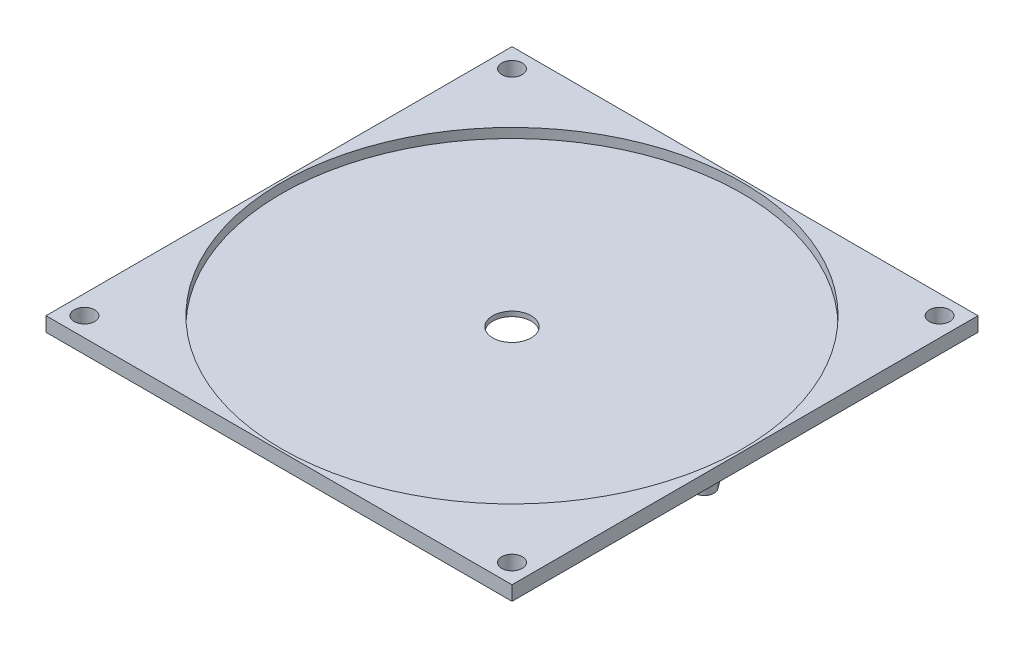
SolidWorks part; units mm, degrees
ref_plane "Front Plane" through (0, 0, 0) normal (0, 0, 1) x (1, 0, 0)
ref_plane "Top Plane" through (0, 0, 0) normal (0, 1, 0) x (1, 0, 0)
ref_plane "Right Plane" through (0, 0, 0) normal (1, 0, 0) x (0, 0, -1)
sketch "Sketch2" plane through (0, 0, 0) normal (0, 1, 0) x (1, 0, 0)
  line L1 (0, 0) -> (154.0002, 0)
  line L2 (0, 0) -> (0, 154.0002)
  line L3 (0, 154.0002) -> (154.0002, 154.0002)
  line L4 (154.0002, 0) -> (154.0002, 154.0002)
  dimension "D1" = 154.0002
  dimension "D2" = 154.0002
extrude "Boss-Extrude1" add sketch "Sketch2" along normal blind 4.7625
sketch "Sketch4" plane through (0, 4.7625, 0) normal (0, 1, 0) x (1, 0, 0)
  line L0 (0, 154.0002) -> (154.0002, 0) construction
  line L1 (0, 0) -> (154.0002, 154.0002) construction
  circle A0 centre (77.0001, 77.0001) radius 76.2
  dimension "D1" = 152.4
extrude "Cut-Extrude1" cut sketch "Sketch4" against normal blind 3.175
sketch "Sketch5" plane through (0, 4.7625, 0) normal (0, 1, 0) x (1, 0, 0)
  line L0 (6.35, 154.0002) -> (6.35, 147.6502) construction
  line L1 (154.0002, 154.0002) -> (0, 154.0002) construction
  line L3 (147.6502, 147.6502) -> (154.0002, 147.6502) construction
  line L4 (0, 154.0002) -> (0, 0) construction
  line L5 (154.0002, 0) -> (154.0002, 154.0002) construction
  line L6 (147.6502, 154.0002) -> (147.6502, 147.6502) construction
  line L7 (0, 147.6502) -> (6.35, 147.6502) construction
  line L8 (0, 6.35) -> (6.35, 6.35) construction
  line L9 (6.35, 6.35) -> (6.35, 0) construction
  line L10 (0, 0) -> (154.0002, 0) construction
  line L11 (147.6502, 0) -> (147.6502, 6.35) construction
  line L12 (147.6502, 6.35) -> (154.0002, 6.35) construction
  circle A0 centre (6.35, 6.35) radius 3.3782
  circle A1 centre (6.35, 147.6502) radius 3.3782
  circle A2 centre (147.6502, 147.6502) radius 3.3782
  circle A3 centre (147.6502, 6.35) radius 3.3782
  dimension "D8" = 6.7564
  dimension "D9" = 6.7564
  dimension "D10" = 6.7564
  dimension "D11" = 6.7564
  dimension "D1" = 6.35
  dimension "D2" = 6.35
  dimension "D3" = 6.35
  dimension "D4" = 6.35
  dimension "D5" = 6.35
  dimension "D6" = 6.35
  dimension "D7" = 6.35
extrude "Cut-Extrude2" cut sketch "Sketch5" against normal through all
sketch "Sketch7" plane through (0, 0, 0) normal (0, -1, 0) x (1, 0, 0)
  line L2 (96.0521, -88.4109) -> (110.1169, -69.3609)
  line L3 (109.2842, -89.7001) -> (123.349, -89.7001)
  line L4 (126.524, -86.5251) -> (126.524, -67.4751)
  line L5 (120.7947, -65.5893) -> (106.7299, -84.6393)
  line L6 (109.2842, -89.7001) -> (123.349, -89.7001)
  line L7 (126.524, -86.5251) -> (126.524, -67.4751)
  line L8 (120.7947, -65.5893) -> (106.7299, -84.6393)
  line L9 (150.1137, -64.3001) -> (136.049, -64.3001)
  line L10 (132.874, -67.4751) -> (132.874, -86.5251)
  line L11 (138.6032, -88.4109) -> (152.668, -69.3609)
  line L12 (150.1137, -64.3001) -> (136.049, -64.3001)
  line L13 (132.874, -67.4751) -> (132.874, -86.5251)
  line L14 (138.6032, -88.4109) -> (152.668, -69.3609)
  line L15 (107.5626, -64.3001) -> (93.4979, -64.3001)
  line L16 (96.0521, -88.4109) -> (110.1169, -69.3609)
  line L17 (107.5626, -64.3001) -> (93.4979, -64.3001)
  line L18 (58.2758, -65.2116) -> (38.9091, -84.2616)
  line L19 (25.2516, -88.7886) -> (44.6183, -69.7386)
  line L20 (42.3918, -64.3001) -> (23.0251, -64.3001)
  line L21 (19.8501, -67.4751) -> (19.8501, -86.5251)
  line L22 (25.2516, -88.7886) -> (44.6183, -69.7386)
  line L23 (42.3918, -64.3001) -> (23.0251, -64.3001)
  line L24 (19.8501, -67.4751) -> (19.8501, -86.5251)
  line L25 (41.1355, -89.7001) -> (60.5023, -89.7001)
  line L26 (58.2758, -65.2116) -> (38.9091, -84.2616)
  line L27 (41.1355, -89.7001) -> (60.5023, -89.7001)
  arc A4 (106.7299, -84.6393) -> (109.2842, -89.7001) centre (109.2842, -86.5251) ccw
  arc A5 (123.349, -89.7001) -> (126.524, -86.5251) centre (123.349, -86.5251) ccw
  arc A6 (126.524, -67.4751) -> (120.7947, -65.5893) centre (123.349, -67.4751) ccw
  arc A7 (106.7299, -84.6393) -> (109.2842, -89.7001) centre (109.2842, -86.5251) ccw
  arc A8 (123.349, -89.7001) -> (126.524, -86.5251) centre (123.349, -86.5251) ccw
  arc A9 (126.524, -67.4751) -> (120.7947, -65.5893) centre (123.349, -67.4751) ccw
  arc A11 (152.668, -69.3609) -> (150.1137, -64.3001) centre (150.1137, -67.4751) ccw
  arc A12 (136.049, -64.3001) -> (132.874, -67.4751) centre (136.049, -67.4751) ccw
  arc A13 (132.874, -86.5251) -> (138.6032, -88.4109) centre (136.049, -86.5251) ccw
  arc A14 (152.668, -69.3609) -> (150.1137, -64.3001) centre (150.1137, -67.4751) ccw
  arc A15 (136.049, -64.3001) -> (132.874, -67.4751) centre (136.049, -67.4751) ccw
  arc A16 (132.874, -86.5251) -> (138.6032, -88.4109) centre (136.049, -86.5251) ccw
  arc A19 (93.4979, -64.3001) -> (90.7482, -69.0626) centre (93.4979, -67.4751) ccw
  arc A20 (90.7482, -84.9376) -> (90.7482, -69.0626) centre (77.0001, -77.0001) ccw
  arc A21 (90.7482, -84.9376) -> (96.0521, -88.4109) centre (93.4979, -86.5251) ccw
  arc A22 (110.1169, -69.3609) -> (107.5626, -64.3001) centre (107.5626, -67.4751) ccw
  arc A23 (93.4979, -64.3001) -> (90.7482, -69.0626) centre (93.4979, -67.4751) ccw
  arc A24 (90.7482, -84.9376) -> (90.7482, -69.0626) centre (77.0001, -77.0001) ccw
  arc A25 (90.7482, -84.9376) -> (96.0521, -88.4109) centre (93.4979, -86.5251) ccw
  arc A26 (110.1169, -69.3609) -> (107.5626, -64.3001) centre (107.5626, -67.4751) ccw
  arc A27 (19.8501, -86.5251) -> (25.2516, -88.7886) centre (23.0251, -86.5251) ccw
  arc A28 (44.6183, -69.7386) -> (42.3918, -64.3001) centre (42.3918, -67.4751) ccw
  arc A29 (23.0251, -64.3001) -> (19.8501, -67.4751) centre (23.0251, -67.4751) ccw
  arc A30 (19.8501, -86.5251) -> (25.2516, -88.7886) centre (23.0251, -86.5251) ccw
  arc A31 (44.6183, -69.7386) -> (42.3918, -64.3001) centre (42.3918, -67.4751) ccw
  arc A32 (23.0251, -64.3001) -> (19.8501, -67.4751) centre (23.0251, -67.4751) ccw
  arc A35 (60.5023, -89.7001) -> (63.2519, -84.9376) centre (60.5023, -86.5251) ccw
  arc A36 (63.2519, -69.0626) -> (63.2519, -84.9376) centre (77.0001, -77.0001) ccw
  arc A37 (63.2519, -69.0626) -> (58.2758, -65.2116) centre (60.5023, -67.4751) ccw
  arc A38 (38.9091, -84.2616) -> (41.1355, -89.7001) centre (41.1355, -86.5251) ccw
  arc A39 (60.5023, -89.7001) -> (63.2519, -84.9376) centre (60.5023, -86.5251) ccw
  arc A40 (63.2519, -69.0626) -> (63.2519, -84.9376) centre (77.0001, -77.0001) ccw
  arc A41 (63.2519, -69.0626) -> (58.2758, -65.2116) centre (60.5023, -67.4751) ccw
  arc A42 (38.9091, -84.2616) -> (41.1355, -89.7001) centre (41.1355, -86.5251) ccw
  dimension "D1" = 0
  dimension "D2" = 0
  dimension "D3" = 0
  dimension "D4" = 0
  dimension "D5" = 0
extrude "Boss-Extrude2" add sketch "Sketch7" along normal up to surface (3.175 mm away)
sketch "Sketch8" plane through (0, 0, 0) normal (0, -1, 0) x (1, 0, 0)
  circle A0 centre (77.0001, -77.0001) radius 6.35
  dimension "D1" = 12.7
extrude "Cut-Extrude3" cut sketch "Sketch8" against normal through all
